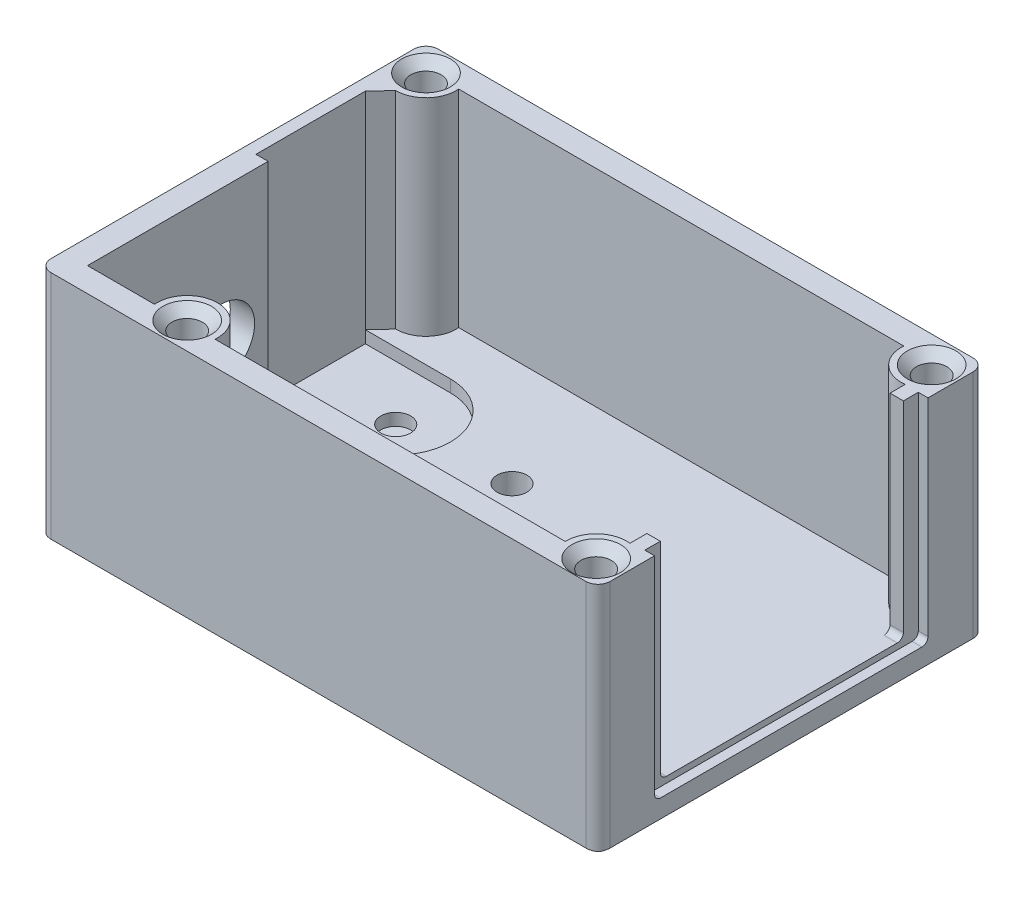
SolidWorks part; units mm, degrees
ref_plane "Front Plane" through (0, 0, 0) normal (0, 0, 1) x (1, 0, 0)
ref_plane "Top Plane" through (0, 0, 0) normal (0, 1, 0) x (1, 0, 0)
ref_plane "Right Plane" through (0, 0, 0) normal (1, 0, 0) x (0, 0, -1)
sketch "Sketch1" plane through (0, 0, 0) normal (0, 1, 0) x (1, 0, 0)
  line L1 (-23, -15.925) -> (23, -15.925)
  line L2 (-23, -15.925) -> (-23, 15.925)
  line L3 (-23, 15.925) -> (23, 15.925)
  line L4 (23, -15.925) -> (23, 15.925)
  line L5 (-23, -15.925) -> (23, 15.925) construction
  line L6 (-23, 15.925) -> (23, -15.925) construction
  point P0 (0, 0)
  dimension "D1" = 31.85
  dimension "D2" = 46
extrude "Boss-Extrude1" add sketch "Sketch1" along normal blind 20
hole_wizard "CSK for M6 Hex Socket Countersunk Cap Screw1" positions "Sketch6" profile "Sketch7" countersink size "M6" standard "ISO"
sketch "Sketch6" plane through (0, 20, 0) normal (0, 1, 0) x (1, 0, 0)
  line L0 (23, -15.925) -> (23, 15.925) construction
  line L1 (23, 15.925) -> (-23, 15.925) construction
  line L2 (-23, -15.925) -> (23, -15.925) construction
  line L3 (-23, 15.925) -> (-23, -15.925) construction
  point P0 (-20.8, 13.725)
  point P2 (-13, -13.725)
  point P4 (20.8, 13.725)
  point P6 (20.8, -13.8769)
  dimension "D1" = 2.2
  dimension "D2" = 2.2
  dimension "D3" = 2.2
  dimension "D4" = 10
  dimension "2.2" = 2.0481
  dimension "D5" = 2.2
  dimension "D6" = 2.2
  dimension "D7" = 2.2
sketch "Sketch7" plane through (-20.8, 20, -13.725) normal (1, 0, 0) x (0, 0, 1)
  line L0 (0, 0) -> (0, 17.7511)
  line L1 (0, 17.7511) -> (1.25, 17)
  line L2 (1.25, 17) -> (1.25, 0.75)
  line L3 (1.25, 0.75) -> (2, 0)
  line L5 (2, 0) -> (0, 0)
  line L6 (-1.25, 0.75) -> (-2, 0) construction
  line L10 (0, 17.7511) -> (-1.25, 17) construction
  line L11 (0, -6.35) -> (0, 107.95) construction
  dimension "Hole Dia." = 2.5
  dimension "Hole Depth" = 17
  dimension "Near C'Sink Dia." = 4
  dimension "Near C'Sink Angle" = 90
  dimension "Drill Angle" = 118
sketch "Sketch8" plane through (0, 20, 0) normal (0, 1, 0) x (1, 0, 0)
  line L0 (-21, 0.935) -> (-22, 0.935)
  line L1 (-22, 0.935) -> (-22, 9.935)
  line L2 (-22, 9.935) -> (-20.8, 11.225)
  line L3 (23, 15.925) -> (-23, 15.925) construction
  line L4 (-23, 15.925) -> (-23, -15.925) construction
  line L7 (21.3, 11.2755) -> (22.2, 11.225)
  line L8 (22.2, -15.925) -> (22.2, 15.925)
  line L9 (-10.508, -13.925) -> (18.3005, -13.925)
  line L10 (22.2, -11.4275) -> (22.2, 11.225)
  line L11 (21.3, -11.4275) -> (22.2, -11.4275)
  line L13 (21, -13.925) -> (21, 13.925)
  line L14 (21, 13.925) -> (-21, 13.925)
  line L15 (-21, 13.925) -> (-21, -13.925)
  line L16 (-21, -13.925) -> (21, -13.925)
  line L18 (18.308, 13.925) -> (-18.308, 13.925)
  line L19 (-21, 0.935) -> (-21, -13.925)
  line L20 (-21, -13.925) -> (-15.492, -13.925)
  circle A2 centre (-20.8, 13.725) radius 2.5
  arc A4 (-20.8, 11.225) -> (-18.308, 13.925) centre (-20.8, 13.725) ccw
  circle A22 centre (20.8, 13.725) radius 2.5
  arc A23 (18.308, 13.925) -> (21.3, 11.2755) centre (20.8, 13.725) ccw
  circle A25 centre (-13, -13.725) radius 2.5
  arc A26 (-10.508, -13.925) -> (-15.492, -13.925) centre (-13, -13.725) ccw
  circle A28 centre (20.8, -13.8769) radius 2.5
  arc A29 (21.3, -11.4275) -> (18.3005, -13.925) centre (20.8, -13.8769) ccw
  point P8 (-21.3577, 11.288)
  point P18 (0, 0)
  point P20 (-20.8, 11.2755)
  dimension "D6" = 0.5
  dimension "D7" = 1
  dimension "D8" = 9
  dimension "D9" = 0.8
  dimension "D1" = 5.99
  dimension "D2" = 0.5
  dimension "D3" = 0.5
  dimension "D4" = 0.5
  dimension "D5" = 2
extrude "Cut-Extrude1" cut sketch "Sketch8" against normal blind 17
sketch "Sketch9" plane through (23, 0, 0) normal (1, 0, 0) x (0, 0, -1)
  line L0 (-15.925, 20) -> (15.925, 20) construction
  line L1 (-11.2741, 20) -> (11.2259, 20)
  line L2 (-11.2741, 20) -> (-11.2741, 2.5)
  line L3 (-11.2741, 2.5) -> (11.2259, 2.5)
  line L4 (11.2259, 20) -> (11.2259, 2.5)
  line L5 (0, 11) -> (0, -11) construction
  dimension "D1" = 22.5
  dimension "D2" = 11.2741
  dimension "D3" = 17.5
extrude "Cut-Extrude2" cut sketch "Sketch9" against normal blind 0.8
fillet "Fillet1" radius 1 4 edges at (-23, 10, 15.925) (-23, 10, -15.925) (23, 10, -15.925) (23, 10, 15.925)
chamfer "Chamfer3" distance 5 distance2 1 1 edges at (23, 0, 0) first distance on face at (0, 0, 0)
chamfer "Chamfer4" distance 5 distance2 1 2 edges at (-2, 0, -15.925) (-2, 0, 15.925) first distance on face at (-9.069, 0, 0)
sketch "Sketch15" plane through (0, 3, 0) normal (0, 1, 0) x (1, 0, 0)
  line L1 (21.1, 11.7109) -> (22.2, 11.7109)
  line L2 (21.1, 11.7109) -> (21.1, 10)
  line L3 (21.1, 10) -> (22.2, 10)
  line L4 (22.2, 11.7109) -> (22.2, 10)
  line L5 (-11, 0) -> (11, 0) construction
  line L6 (21.1, -10) -> (22.2, -10)
  line L7 (22.2, -11.7109) -> (22.2, -10)
  line L8 (21.1, -11.7109) -> (22.2, -11.7109)
  line L9 (21.1, -11.7109) -> (21.1, -10)
  line L10 (22.2, -11.2741) -> (22.2, 11.2259) construction
  dimension "D1" = 20
  dimension "D2" = 1.1
extrude "Boss-Extrude2" add sketch "Sketch15" along normal up to surface (17 mm away) up to face at (2.3935, 20, 0.1209)
fillet "Fillet2" radius 0.5 4 edges at (22.6, 2.5, -11.2259) (21.65, 3, -10) (22.6, 2.5, 11.2741) (21.65, 3, 10)
sketch "Sketch16" plane through (0, 3, 0) normal (0, 1, 0) x (1, 0, 0)
  line L0 (-23, 14.925) -> (-23, -14.925) construction
  line L1 (22, 15.925) -> (-22, 15.925) construction
  line L2 (-11, 0) -> (11, 0) construction
  circle A0 centre (-15, 5.435) radius 1.225
  circle A1 centre (-5, 5) radius 1.225
  circle A2 centre (-5, -5) radius 1.225
  dimension "D1" = 2.45
  dimension "D4" = 2.45
  dimension "D2" = 8
  dimension "D3" = 10.49
  dimension "D5" = 10
  dimension "D6" = 18
extrude "Cut-Extrude5" cut sketch "Sketch16" against normal blind 2
sketch "Sketch17" plane through (0, 3, 0) normal (0, 1, 0) x (1, 0, 0)
  line L0 (-15, 5.435) -> (-30.9936, 5.435) construction
  line L6 (-22, 0.935) -> (-22, 9.935)
  line L7 (-22, 9.935) -> (-22, 0.935) construction
  line L8 (-22, 9.935) -> (-15, 9.935)
  line L9 (-22, 0.935) -> (-15, 0.935)
  arc A1 (-15, 0.935) -> (-15, 9.935) centre (-15, 5.435) ccw
  dimension "D1" = 9
extrude "Cut-Extrude6" cut sketch "Sketch17" against normal blind 1
sketch "Sketch18" plane through (0, 3, 0) normal (0, 1, 0) x (1, 0, 0)
  line L0 (-11, 0) -> (11, 0) construction
  line L3 (23, -10.7741) -> (23, 10.7259) construction
  line L4 (21.1, 10) -> (21.1, 11.2431) construction
  circle A0 centre (7.81, 0) radius 1.225
  circle A1 centre (7.81, 0) radius 3
  dimension "D1" = 15.19
  dimension "D2" = 2.45
  dimension "D3" = 6
extrude "Boss-Extrude3" add sketch "Sketch18" along normal blind 2
sketch "Sketch19" plane through (-21, 0, 0) normal (1, 0, 0) x (0, 0, -1)
  line L0 (0.935, 3) -> (-13.925, 3) construction
  line L3 (-15.925, 1) -> (-15.925, 20) construction
  circle A0 centre (-2.925, 9) radius 2.75
  dimension "D1" = 6
  dimension "D3" = 5.5
  dimension "D2" = 13
extrude "Cut-Extrude7" cut sketch "Sketch19" against normal through all
sketch "Sketch20" plane through (0, 0, 0) normal (0, -1, 0) x (1, 0, 0)
  circle A0 centre (7.81, 0) radius 3 construction
  circle A1 centre (7.81, 0) radius 3 construction
  circle A2 centre (7.81, 0) radius 6.5
  dimension "D1" = 13
extrude "Boss-Extrude4" add sketch "Sketch20" along normal blind 0.5
